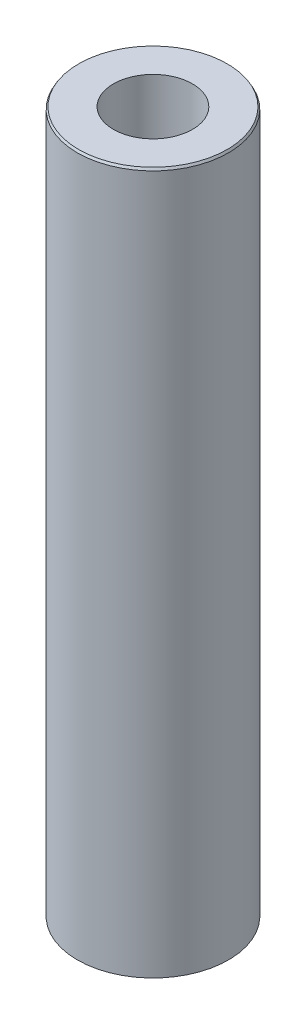
SolidWorks part; units mm, degrees
ref_plane "Front Plane" through (0, 0, 0) normal (0, 0, 1) x (1, 0, 0)
ref_plane "Top Plane" through (0, 0, 0) normal (0, 1, 0) x (1, 0, 0)
ref_plane "Right Plane" through (0, 0, 0) normal (1, 0, 0) x (0, 0, -1)
sketch "Sketch1" plane through (0, 0, 0) normal (0, 1, 0) x (1, 0, 0)
  circle A0 centre (0, 0) radius 12.5
  dimension "SHAFT_OD" = 25
extrude "Boss-Extrude1" add sketch "Sketch1" along normal blind 116.207
sketch "Sketch2" plane through (0, 0, 0) normal (0, 1, 0) x (1, 0, 0)
  circle A0 centre (0, 0) radius 6.5377
  dimension "BORE_D" = 13.0754
extrude "Cut-Extrude1" cut sketch "Sketch2" along normal through all
chamfer "Chamfer1" distance 0.3711 angle 30 2 edges at (0, 116.207, 12.5) (0, 0, 12.5) first distance on face at (0, 116.207, 12.5) first distance on face at (0, 0, 6.5377)
